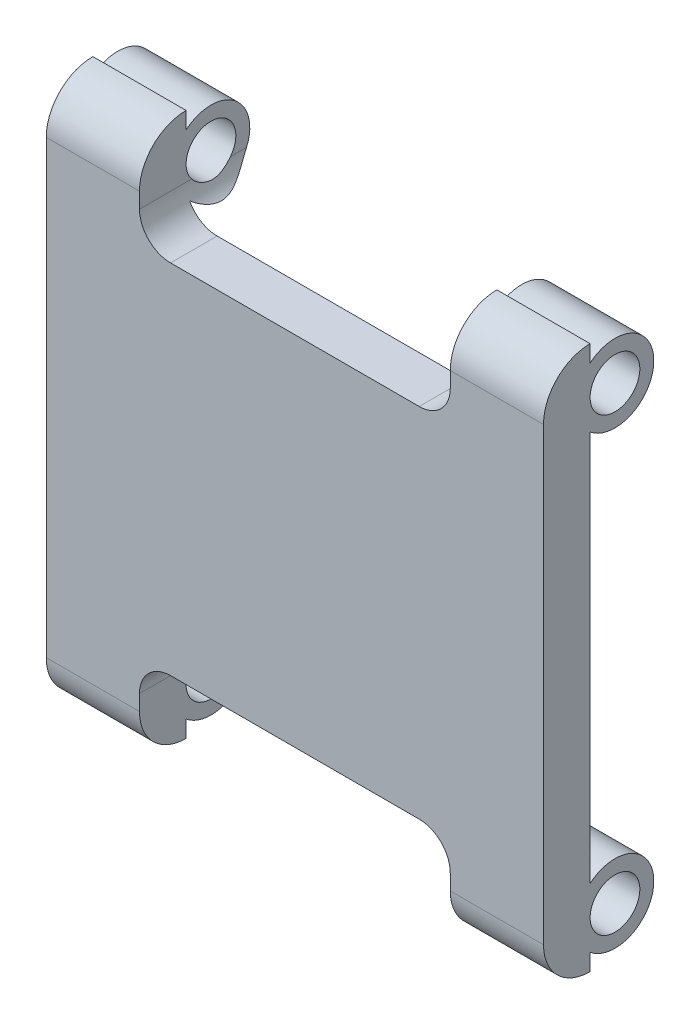
SolidWorks part; units mm, degrees
ref_plane "Front Plane" through (0, 0, 0) normal (0, 0, 1) x (1, 0, 0)
ref_plane "Top Plane" through (0, 0, 0) normal (0, 1, 0) x (1, 0, 0)
ref_plane "Right Plane" through (0, 0, 0) normal (1, 0, 0) x (0, 0, -1)
sketch "Sketch1" plane through (0, 0, 0) normal (0, 0, 1) x (1, 0, 0)
  line L0 (-16, 35) -> (-16, 0)
  line L1 (-16, 0) -> (16, 0)
  line L7 (-16, 35) -> (16, 35)
  line L8 (16, 35) -> (16, 0)
  point P0 (0, 0)
  point P1 (0, 0)
  point P6 (0, 35)
  dimension "D1" = 32
  dimension "D2" = 32
  dimension "D3" = 35
  dimension "D4" = 35
extrude "Boss-Extrude1" add sketch "Sketch1" along normal blind 3
sketch "Sketch4" plane through (0, 0, 0) normal (1, 0, 0) x (0, 0, -1)
  line L0 (-3, 0) -> (0, 0) construction
  line L1 (0, 0) -> (0, 35) construction
  line L2 (-3, 35) -> (0, 35) construction
  circle A0 centre (1.6, 32) radius 1.6
  circle A1 centre (1.6, 32) radius 2.5
  circle A2 centre (1.6, 3) radius 2.5
  circle A3 centre (1.6, 3) radius 1.6
  dimension "D1" = 3.2
  dimension "D2" = 5
  dimension "D3" = 3.2
  dimension "D4" = 5
  dimension "D5" = 3
  dimension "D6" = 3
extrude "Boss-Extrude2" add sketch "Sketch4" along normal up to surface and the other way up to surface up to face at (16, 17.5, 1.5) other way up to face at (-16, 17.5, 1.5)
sketch "Sketch5" plane through (0, 0, 3) normal (0, 0, 1) x (1, 0, 0)
  line L0 (-10, 35) -> (-10, 31)
  line L1 (16, 35) -> (-16, 35) construction
  line L2 (-8, 29) -> (8, 29)
  line L3 (10, 31) -> (10, 35)
  line L4 (-10, 0) -> (-10, 4)
  line L5 (-16, 0) -> (16, 0) construction
  line L6 (-8, 6) -> (8, 6)
  line L7 (10, 4) -> (10, 0)
  line L8 (10, 0) -> (-10, 0)
  line L9 (10, 35) -> (-10, 35)
  arc A0 (8, 6) -> (10, 4) centre (8, 4) cw
  arc A1 (-10, 4) -> (-8, 6) centre (-8, 4) cw
  arc A2 (8, 29) -> (10, 31) centre (8, 31) ccw
  arc A3 (-10, 31) -> (-8, 29) centre (-8, 31) ccw
  point P10 (0, 6)
  point P17 (10, 6)
  point P22 (10, 29)
  point P25 (-10, 29)
  dimension "D5" = 2
  dimension "D1" = 20
  dimension "D2" = 20
  dimension "D3" = 6
  dimension "D4" = 6
extrude "Cut-Extrude1" cut sketch "Sketch5" against normal through all contours L9 L0 A3 L2 A2 L3 | L8 L4 A1 L6 A0 L7
fillet "Fillet1" radius 3 4 edges at (13, 0, 3) (-13, 0, 3) (13, 35, 3) (-13, 35, 3)
